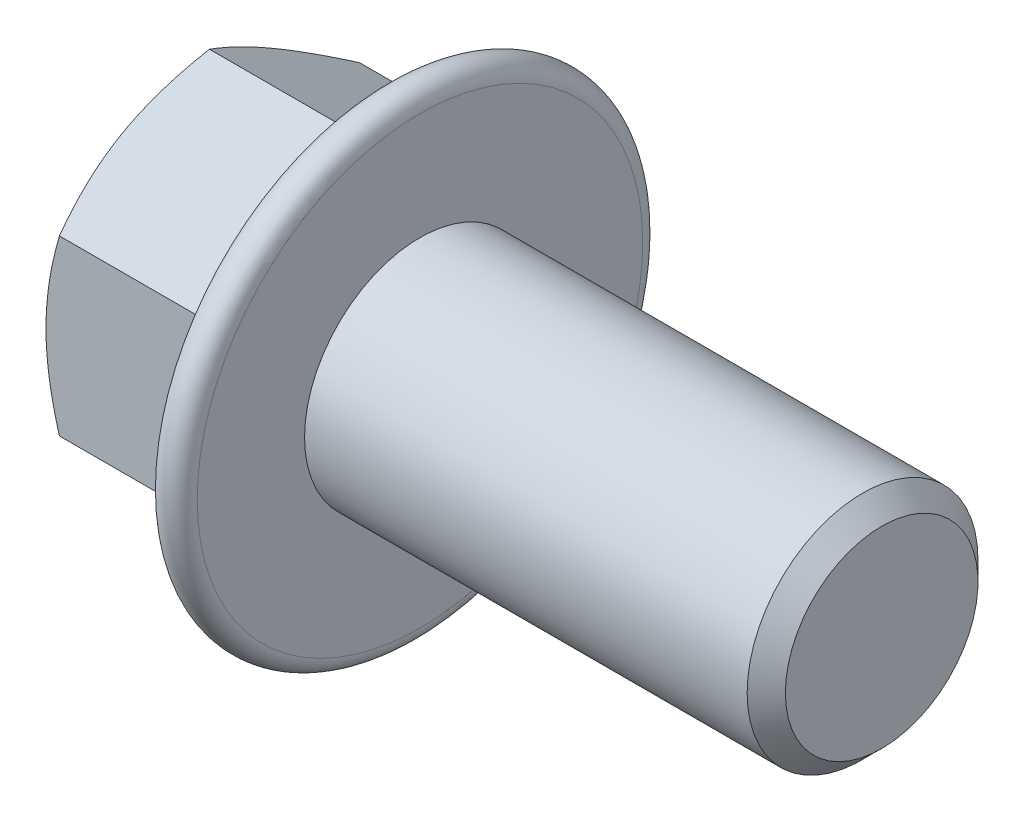
SolidWorks part; units mm, degrees
extrude "BaseHead" add sketch "Sketch1" along normal blind 9.7
sketch "Sketch1" plane through (0, 0, 0) normal (1, 0, 0) x (0, 0, -1)
  line L0 (6.5, 3.7528) -> (6.5, -3.7528)
  line L1 (-6.5, 3.7528) -> (-6.5, -3.7528)
  line L2 (6.5, -3.7528) -> (0, -7.5056)
  line L3 (0, -7.5056) -> (-6.5, -3.7528)
  line L4 (6.5, 3.7528) -> (0, 7.5056)
  line L5 (0, 7.5056) -> (-6.5, 3.7528)
  dimension "D2" = 120
  dimension "D3" = 6.5
  dimension "D4" = 6.5
  dimension "D5" = 6.5
ref_plane "Plane1" through (0, 0, 0) normal (0, 0, 1) x (1, 0, 0)
ref_plane "Plane2" through (0, 0, 0) normal (0, 1, 0) x (1, 0, 0)
ref_plane "Plane3" through (0, 0, 0) normal (1, 0, 0) x (0, 0, -1)
sketch "BodySke" plane through (0, 0, 0) normal (0, 0, 1) x (1, 0, 0)
  line L0 (0, 3.7528) -> (0, -3.7528) construction
  line L1 (0, 0) -> (29.7, 0)
  line L2 (0, 0) -> (0, 5)
  line L3 (0, 5) -> (28.872, 5)
  line L4 (29.7, 0) -> (29.7, 4.172)
  line L5 (9.7, 7.5056) -> (9.7, 3.7528) construction
  line L6 (29.7, 4.172) -> (28.872, 5)
  line L7 (0, 0) -> (96.52, 0) construction
  line L8 (29.7, -4.172) -> (28.872, -5) construction
  line L9 (0, -5) -> (28.872, -5) construction
  line L10 (11.2, 15.24) -> (11.2, -1.27) construction
  line L11 (9.7, 15.24) -> (9.7, -1.27) construction
  line L12 (9.7, 3.7528) -> (9.7, -3.7528) construction
  dimension "Diameter" = 10
revolve "BaseBody" add sketch "BodySke"
cosmetic thread "ThreadCosmetic" [suppressed]
fillet "HeadFillet" [suppressed] radius 0.4
sketch "Sketch3" plane through (0, 0, 0) normal (0, 0, 1) x (1, 0, 0)
  line L0 (0, 6.5) -> (3.4673, 12.5056)
  line L1 (0, 7.5056) -> (0, 3.7528) construction
  line L2 (3.4673, 12.5056) -> (3.4673, 17.5056)
  line L3 (3.4673, 17.5056) -> (-10, 17.5056)
  line L4 (-10, 17.5056) -> (-10, 6.5)
  line L5 (-10, 6.5) -> (0, 6.5)
  line L6 (0, 0) -> (99.06, 0) construction
  line L7 (9.7, 7.5056) -> (0, 7.5056) construction
  dimension "D1" = 6.5
  dimension "D2" = 5
  dimension "D3" = 10
  dimension "D4" = 5
  dimension "Head_ch_ang" = 30
revolve "HeadChamfer" cut sketch "Sketch3" angle 360 about L6
sketch "Sketch4" plane through (0, 0, 0) normal (0, 0, 1) x (1, 0, 0)
  line L0 (4.6396, 0) -> (8.2452, 9.9065)
  line L1 (9.7, 7.5056) -> (9.7, 3.7528) construction
  line L2 (8.2, 34.3444) -> (8.2, 16.9779) construction
  line L3 (9.7, 0) -> (9.7, 9.65)
  line L4 (8.3021, 10.4) -> (20.1618, 10.4) construction
  line L5 (0, 0) -> (95.25, 0) construction
  line L6 (0, 0) -> (96.52, 0) construction
  line L7 (4.6396, 0) -> (9.7, 0)
  line L8 (8.3021, -10.4) -> (20.1618, -10.4) construction
  arc A0 (9.7, 9.65) -> (8.2452, 9.9065) centre (8.95, 9.65) ccw
  dimension "D1" = 20
  dimension "Flange_thickness" = 1.5
  dimension "Flange_dia" = 20.8
revolve "Flange" add sketch "Sketch4" angle 360 about L5
fillet "FlangeHexFillet" radius 0.2 6 edges
sketch "ThdSchSke" plane through (0, 0, 0) normal (0, 0, 1) x (1, 0, 0)
  line L0 (11.2, -4.172) -> (10.6202, -5)
  line L1 (11.2, -4.172) -> (11.7798, -5)
  line L2 (11.7798, -5) -> (11.7798, -6.25)
  line L3 (-3.175, 0) -> (5.1513, 0) construction
  line L5 (11.7798, -6.25) -> (10.6202, -6.25)
  line L6 (10.6202, -6.25) -> (10.6202, -5)
  dimension "Thread_minor" = 8.344
  dimension "Diameter" = 10
  dimension "Start" = 11.2
revolve "ThreadSchematic" [suppressed] cut sketch "ThdSchSke" angle 360 about L3
pattern_linear "ThdSchPat" [suppressed]
equation "\"D3@Sketch1\" = \"Width_flats@Sketch1\" / 2"
equation "\"D4@Sketch1\" = \"D3@Sketch1\""
equation "\"D5@Sketch1\" = \"D4@Sketch1\""
equation "\"Thread_minor@ThreadCosmetic\" = \"Minor_dia@BodySke\""
equation "\"D1@Sketch3\" = \"Width_flats@Sketch1\" / 2"
equation "\"Thread_length@ThreadCosmetic\" = ((sgn( (\"Length@BodySke\" - \"Advance@BodySke\" ) - \"Thread_nom@BodySke\" )-1)*( (\"Length@BodySke\" - \"Advance@BodySke\" ) - \"Thread_nom@BodySke\" ))/-2+ \"Thread_nom@BodySke\""
equation "\"Thread_minor@ThdSchSke\" = \"Minor_dia@BodySke\""
equation "\"Diameter@ThdSchSke\" = \"Diameter@BodySke\""
equation "\"Overcut@ThdSchSke\" = \"Diameter@BodySke\" * 1.25"
equation "\"Start@ThdSchSke\" = \"Head_ht@BaseHead\" + \"Length@BodySke\" - \"Thread_length@ThreadCosmetic\"  '---Non-countersunk---"
equation "\"Num_threads@ThdSchPat\" = int( \"Thread_length@ThreadCosmetic\" / \"Advance@BodySke\" + 0.999 )  + 1"
equation "\"Advance@ThdSchPat\" = \"Thread_length@ThreadCosmetic\" /  (\"Num_threads@ThdSchPat\" - 1) 'relax it"
equation "\"Num_threads@ThdSchPat\" = \"Num_threads@ThdSchPat\" - sgn( \"Num_threads@ThdSchPat\" - 1) '---chamfered tips only---"
